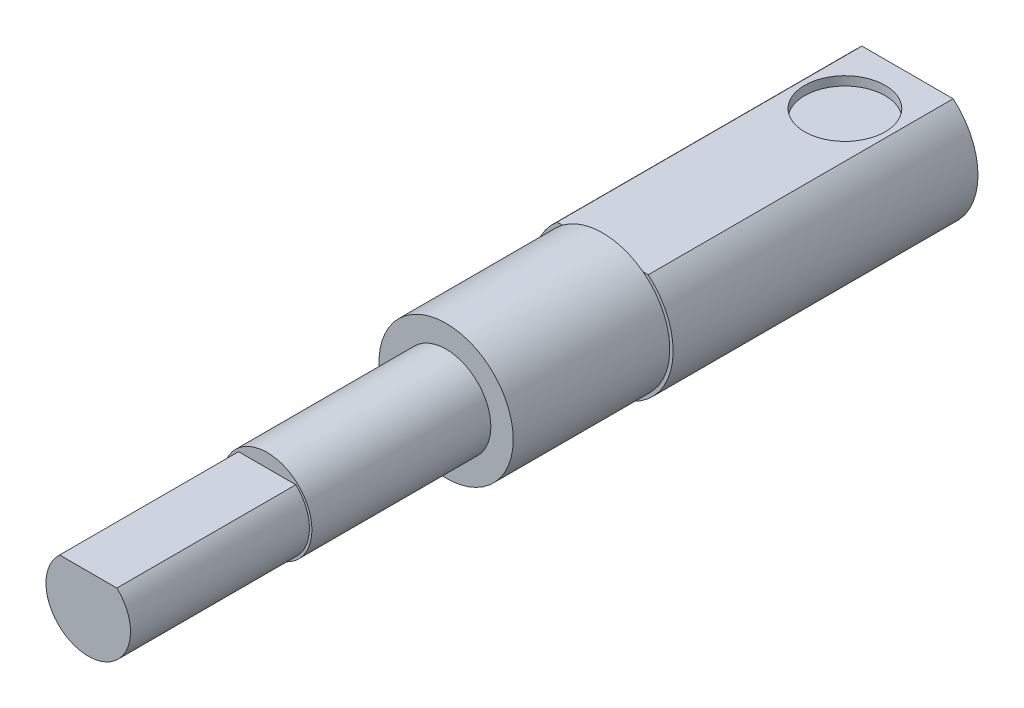
SolidWorks part; units mm, degrees
material "ASTM A36 Steel"
ref_plane "Front" through (0, 0, 0) normal (0, 0, 1) x (1, 0, 0)
ref_plane "Top" through (0, 0, 0) normal (0, 1, 0) x (1, 0, 0)
ref_plane "Right" through (0, 0, 0) normal (1, 0, 0) x (0, 0, -1)
sketch "Sketch1" plane through (0, 0, 0) normal (0, 0, 1) x (1, 0, 0)
  circle A0 centre (0, 0) radius 5
  dimension "D1" = 10
extrude "Boss-Extrude1" add sketch "Sketch1" along normal blind 21.6375
sketch "Sketch2" plane through (0, 0, 21.6375) normal (0, 0, 1) x (1, 0, 0)
  circle A0 centre (0, 0) radius 4.7625
  dimension "D1" = 9.525
extrude "Boss-Extrude2" add sketch "Sketch2" along normal blind 11.1125
sketch "Sketch3" plane through (0, 0, 32.75) normal (0, 0, 1) x (1, 0, 0)
  circle A0 centre (0, 0) radius 3.175
  dimension "D1" = 6.35
extrude "Boss-Extrude3" add sketch "Sketch3" along normal blind 12.7
sketch "Sketch4" plane through (0, 0, 0) normal (0, 0, -1) x (-1, 0, 0)
  line L0 (0, 0) -> (0, 5) construction
  line L2 (12.7, 3.8094) -> (-12.7, 3.8094)
  line L3 (12.7, 3.8094) -> (12.7, 6.1906)
  line L4 (12.7, 6.1906) -> (-12.7, 6.1906)
  line L5 (-12.7, 3.8094) -> (-12.7, 6.1906)
  line L6 (12.7, 3.8094) -> (-12.7, 6.1906) construction
  line L7 (12.7, 6.1906) -> (-12.7, 3.8094) construction
  circle A0 centre (0, 0) radius 5 construction
  dimension "D1" = 2.3813
  dimension "D2" = 25.4
extrude "Cut-Extrude1" cut sketch "Sketch4" against normal up to surface (21.6375 mm away) up to face at (4.7625, 0, 21.6375)
sketch "Sketch5" plane through (0, 0, 45.45) normal (0, 0, 1) x (1, 0, 0)
  line L0 (0, 0) -> (0, 3.175) construction
  line L2 (12.7, 2.3813) -> (-12.7, 2.3812)
  line L3 (12.7, 2.3813) -> (12.7, 3.9688)
  line L4 (12.7, 3.9688) -> (-12.7, 3.9687)
  line L5 (-12.7, 2.3812) -> (-12.7, 3.9687)
  line L6 (12.7, 2.3813) -> (-12.7, 3.9687) construction
  line L7 (12.7, 3.9688) -> (-12.7, 2.3812) construction
  circle A0 centre (0, 0) radius 3.175 construction
  dimension "D1" = 1.5875
  dimension "D2" = 25.4
sketch "Sketch6" plane through (0, 0, 45.45) normal (0, 0, 1) x (1, 0, 0)
  circle A0 centre (0, 0) radius 3
  dimension "D1" = 6
extrude "Boss-Extrude4" add sketch "Sketch6" along normal blind 12.7
sketch "Sketch7" plane through (0, 0, 58.15) normal (0, 0, 1) x (1, 0, 0)
  line L0 (0, 0) -> (0, 3) construction
  line L2 (12.6863, 2.2063) -> (-12.6863, 2.2062)
  line L3 (12.6863, 2.2063) -> (12.6863, 3.7938)
  line L4 (12.6863, 3.7938) -> (-12.6863, 3.7937)
  line L5 (-12.6863, 2.2062) -> (-12.6863, 3.7937)
  line L6 (12.6863, 2.2063) -> (-12.6863, 3.7937) construction
  line L7 (12.6863, 3.7938) -> (-12.6863, 2.2062) construction
  circle A0 centre (0, 0) radius 3 construction
  dimension "D1" = 1.5875
  dimension "D2" = 25.3725
extrude "Cut-Extrude3" cut sketch "Sketch7" against normal up to surface (12.7 mm away) up to face at (3, 0, 45.45)
sketch "Sketch8" plane through (0, 3.8094, 0) normal (0, 1, 0) x (1, 0, 0)
  line L0 (0, -4.445) -> (0, 0) construction
  line L1 (-3.2386, 0) -> (3.2386, 0) construction
  circle A0 centre (0, -4.445) radius 2.8575
  dimension "D2" = 5.715
  dimension "D1" = 4.445
extrude "Cut-Extrude4" cut sketch "Sketch8" against normal blind 0.635
